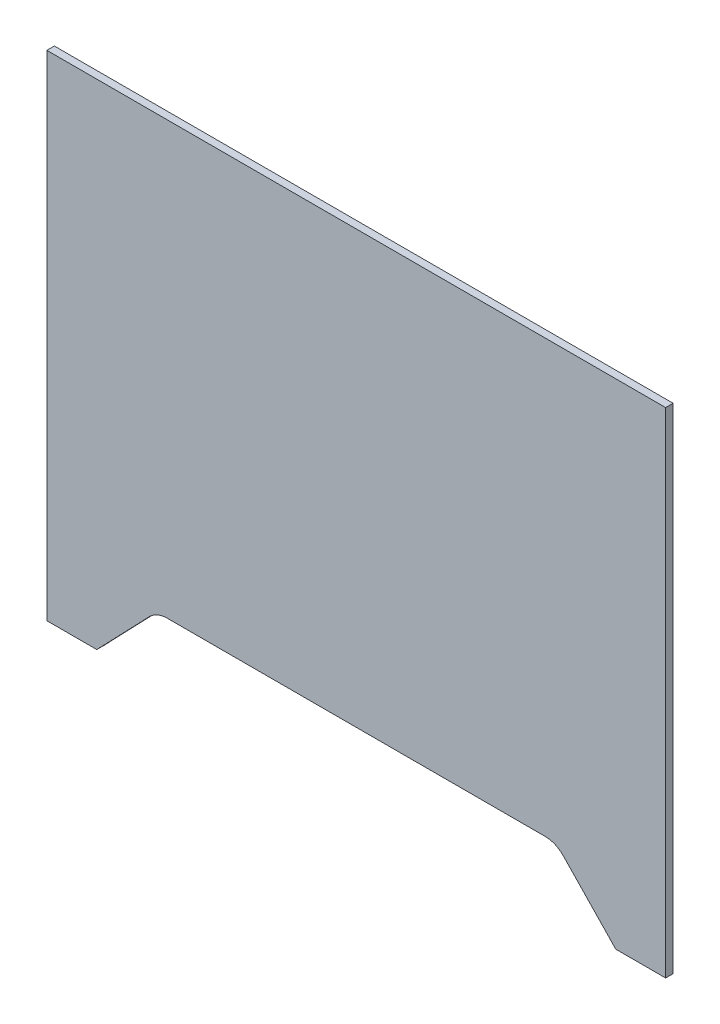
SolidWorks part; units mm, degrees
ref_plane "前视基准面" through (0, 0, 0) normal (0, 0, 1) x (1, 0, 0)
ref_plane "上视基准面" through (0, 0, 0) normal (0, 1, 0) x (1, 0, 0)
ref_plane "右视基准面" through (0, 0, 0) normal (1, 0, 0) x (0, 0, -1)
sketch "Sketch1" plane through (0, 0, 0) normal (0, 0, 1) x (1, 0, 0)
  line L0 (0, -99) -> (0, 0) construction
  line L1 (-124, -99) -> (124, -99) construction
  line L2 (-124, -99) -> (-124, 99)
  line L3 (-124, 99) -> (124, 99)
  line L4 (124, -99) -> (124, 99)
  line L5 (-124, -99) -> (124, 99) construction
  line L6 (-124, 99) -> (124, -99) construction
  line L7 (-75.7378, -74) -> (75.7378, -74)
  line L8 (82.9517, -77.0747) -> (104, -99)
  line L9 (104, -99) -> (124, -99)
  line L10 (-104, -99) -> (-124, -99)
  line L11 (-82.9517, -77.0747) -> (-104, -99)
  arc A0 (82.9517, -77.0747) -> (75.7378, -74) centre (75.7378, -84) ccw
  arc A1 (-82.9517, -77.0747) -> (-75.7378, -74) centre (-75.7378, -84) cw
  point P0 (0, 0)
  point P13 (80, -74)
  point P18 (0, -74)
  dimension "D6" = 10
  dimension "D1" = 248
  dimension "D2" = 198
  dimension "D3" = 25
  dimension "D4" = 20
  dimension "D5" = 80
extrude "Boss-Extrude1" add sketch "Sketch1" along normal blind 3
